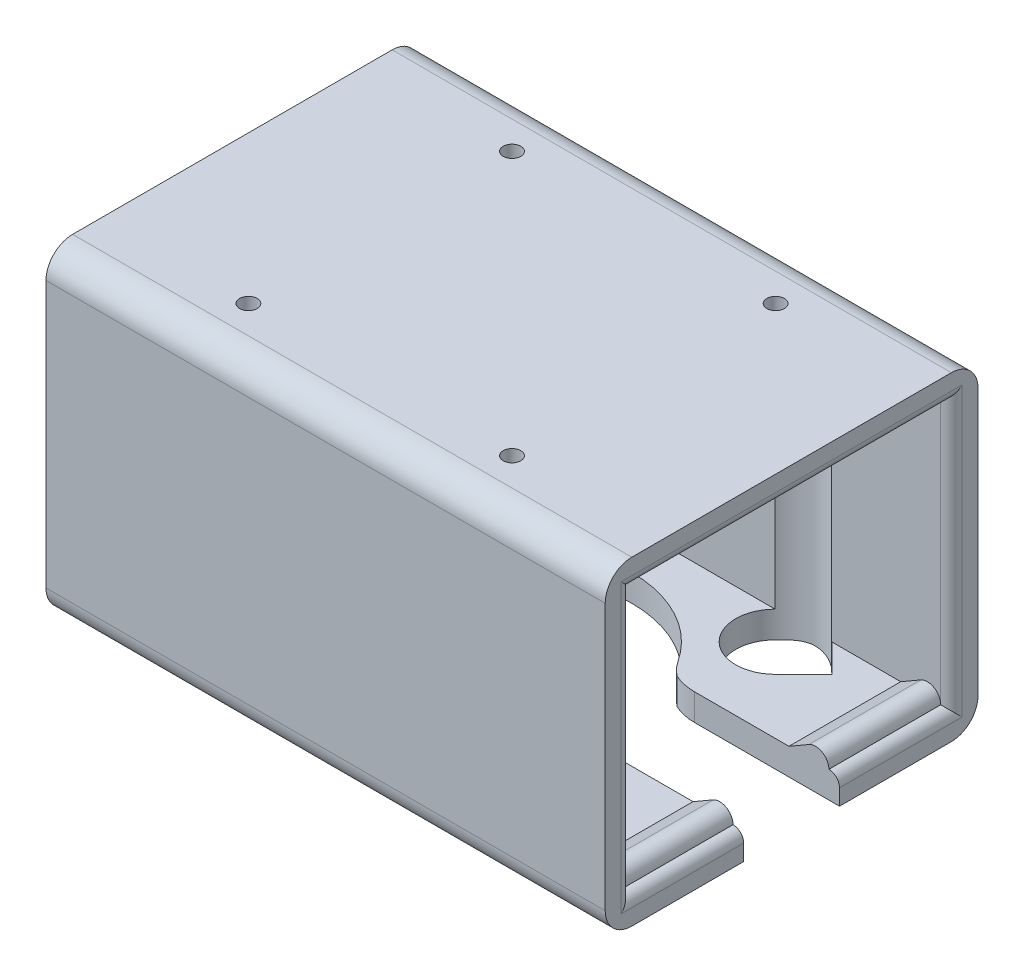
SolidWorks part; units mm, degrees
ref_plane "前视基准面" through (0, 0, 0) normal (0, 0, 1) x (1, 0, 0)
ref_plane "上视基准面" through (0, 0, 0) normal (0, 1, 0) x (1, 0, 0)
ref_plane "右视基准面" through (0, 0, 0) normal (1, 0, 0) x (0, 0, -1)
other "Configuration Table"
sketch "草图1" plane through (0, 0, 0) normal (0, 1, 0) x (1, 0, 0)
  line L0 (47.5, 30) -> (47.5, -30)
  line L1 (-47.5, -30) -> (47.5, -30)
  line L2 (-47.5, -30) -> (-47.5, 30)
  line L3 (-47.5, 30) -> (47.5, 30)
  line L5 (-47.5, -30) -> (47.5, 30) construction
  line L6 (-47.5, 30) -> (47.5, -30) construction
  line L7 (-20, -9) -> (20, -9)
  line L8 (-20, -9) -> (-20, 9)
  line L9 (-20, 9) -> (20, 9)
  line L10 (20, -9) -> (20, 9)
  line L11 (-20, -9) -> (20, 9) construction
  line L12 (-20, 9) -> (20, -9) construction
  line L17 (47.5, 30) -> (47.5, 35)
  line L18 (12.4677, 9) -> (47.5, 9)
  line L19 (12.4677, 9) -> (12.4677, -9)
  line L20 (12.4677, -9) -> (47.5, -9)
  line L21 (47.5, 9) -> (47.5, -9)
  line L22 (52.5, -35) -> (-52.5, -35)
  line L23 (52.5, -35) -> (52.5, 35)
  line L24 (52.5, 35) -> (-52.5, 35)
  line L25 (-52.5, -35) -> (-52.5, 35)
  line L26 (52.5, -35) -> (-52.5, 35) construction
  line L27 (52.5, 35) -> (-52.5, -35) construction
  line L28 (25.5014, 9) -> (52.5, 9)
  line L29 (25.5014, 9) -> (25.5014, -9)
  line L30 (25.5014, -9) -> (52.5, -9)
  line L31 (52.5, 9) -> (52.5, -9)
  line L32 (47.5, -30) -> (47.5, -35)
  line L33 (47.5, 30) -> (52.5, 30)
  line L34 (47.5, -30) -> (52.5, -30)
  point P0 (0, 0)
  point P6 (0, 0)
  point P11 (20, 0)
  point P16 (0, 0)
  dimension "D1" = 95
  dimension "D2" = 60
  dimension "D3" = 20
  dimension "D4" = 18
  dimension "D5" = 5
  dimension "D6" = 5
extrude "凸台-拉伸1" add sketch "草图1" along normal blind 5 contours L20 L7 L8 L9 L18 L0 L3 L2 L1 | L30 L0 L1 L2 L3 L28 L23 L24 L25 L22 | L17 L33 L23 L24 | L34 L32 L22 L23 | L33 L0 L28 L23 | L0 L34 L23 L30 region at (50, 0, -19.5) region at (46.3764, 0, -19.5) region at (0, 0, -31.2207) region at (50, 0, -32.5) region at (50, 0, 19.5) region at (50, 0, 32.5)
sketch "草图3" plane through (0, 5, 0) normal (0, 1, 0) x (1, 0, 0)
  line L0 (52.5, 9) -> (52.5, 35) construction
  line L1 (-52.5, 35) -> (52.5, 35)
  line L2 (-52.5, 35) -> (-52.5, 30)
  line L3 (-52.5, 30) -> (52.5, 30)
  line L4 (52.5, 35) -> (52.5, 30)
  line L5 (52.5, -35) -> (-52.5, -35) construction
  line L6 (-52.5, 35) -> (-47.5, 35)
  line L7 (-52.5, 35) -> (-52.5, -35)
  line L8 (-52.5, -35) -> (-47.5, -35)
  line L9 (-47.5, 35) -> (-47.5, -35)
  line L11 (-52.5, -30) -> (52.5, -30)
  line L12 (-52.5, -30) -> (-52.5, -35)
  line L13 (-52.5, -35) -> (52.5, -35)
  line L14 (52.5, -30) -> (52.5, -35)
  line M11 (52.5, 9) -> (52.5, 35)
  line M12 (52.5, 35) -> (-52.5, 35)
  line M13 (-52.5, 35) -> (-52.5, -35)
  line M14 (-52.5, -35) -> (52.5, -35)
  line M15 (52.5, -35) -> (52.5, -9)
  dimension "D1" = 5
  dimension "D2" = 5
  dimension "D3" = 5
extrude "凸台-拉伸2" add sketch "草图3" along normal blind 55 contours L9 L3 M12 M11 | L9 L1 L3 M13 | L11 L9 L3 M13 | L11 L9 M14 M15 | L11 L7 L9 M14 region at (-50, 5, -32.5) region at (2.5, 5, -32.5) region at (-50, 5, 0) region at (-50, 5, 32.5) region at (2.5, 5, 32.5)
sketch "草图4" plane through (-47.5, 0, 0) normal (1, 0, 0) x (0, 0, -1)
  line L0 (30, 60) -> (30, 5) construction
  line L1 (-30, 60) -> (30, 60)
  line L2 (-30, 60) -> (-30, 55)
  line L3 (-30, 55) -> (30, 55)
  line L4 (30, 60) -> (30, 55)
  dimension "D1" = 5
extrude "凸台-拉伸3" add sketch "草图4" along normal blind 100
sketch "草图5" plane through (0, 0, 0) normal (0, -1, 0) x (1, 0, 0)
  line L0 (0, 22.5) -> (22.5, 9)
  line L1 (-20, 9) -> (52.5, 9) construction
  line L2 (0, -22.5) -> (22.5, -9)
  line L3 (-20, -9) -> (52.5, -9) construction
  line L4 (22.5, -9) -> (22.5, 9)
  circle A0 centre (0, 0) radius 22.5
  line M3 (52.5, -9) -> (-20, -9)
  line M4 (-20, -9) -> (-20, 9)
  line M5 (-20, 9) -> (52.5, 9)
  dimension "D1" = 45
extrude "切除-拉伸1" cut sketch "草图5" against normal up to next contours L2 A0 L0 M3 M4 M5 | A0 L0 M5 | A0 L2 M3 | L0 A0 | L2 A0 region at (10.5905, 0, 17.6509) region at (9.6058, 0, 16.0097) region at (21.0019, 0, 9.5257) region at (10.5905, 0, -17.6509) region at (21.0019, 0, -9.5257)
fillet "圆角2" radius 10 2 edges at (19.8529, 2.5, 10.5882) (22.5, 2.5, 9)
fillet "圆角3" radius 10 2 edges at (22.5, 2.5, -9) (19.8529, 2.5, -10.5882)
fillet "圆角4" radius 5 4 edges at (0, 60, -35) (0, 0, -35) (0, 0, 35) (0, 60, 35)
fillet "圆角5" radius 2 5 edges at (52.5, 30, -30) (52.5, 30, 30) (52.5, 55, 0) (52.5, 5, 19.5) (52.5, 5, -19.5)
sketch "草图6" plane through (0, 55, 0) normal (0, -1, 0) x (1, 0, 0)
  line L1 (-24.75, -24.75) -> (24.75, -24.75)
  line L2 (-24.75, -24.75) -> (-24.75, 24.75)
  line L3 (-24.75, 24.75) -> (24.75, 24.75)
  line L4 (24.75, -24.75) -> (24.75, 24.75)
  line L5 (-24.75, -24.75) -> (24.75, 24.75) construction
  line L6 (-24.75, 24.75) -> (24.75, -24.75) construction
  circle A0 centre (-24.75, 24.75) radius 1.65
  circle A1 centre (24.75, 24.75) radius 1.65
  circle A2 centre (24.75, -24.75) radius 1.65
  circle A3 centre (-24.75, -24.75) radius 1.65
  point P0 (0, 0)
  dimension "D3" = 3.3
  dimension "D4" = 3.3
  dimension "D5" = 3.3
  dimension "D6" = 3.3
  dimension "D1" = 49.5
  dimension "D2" = 49.5
extrude "切除-拉伸2" cut sketch "草图6" against normal up to next contours A0 | A3 | A2 | A1
sketch "草图7" plane through (0, 0, 0) normal (0, -1, 0) x (1, 0, 0)
  line L0 (24.75, 24.75) -> (30.1061, 30)
  line L1 (-24.75, -24.75) -> (24.75, -24.75)
  line L2 (-24.75, -24.75) -> (-24.75, 24.75)
  line L3 (-24.75, 24.75) -> (24.75, 24.75)
  line L4 (24.75, -24.75) -> (24.75, 24.75)
  line L5 (-24.75, -24.75) -> (24.75, 24.75) construction
  line L6 (-24.75, 24.75) -> (24.75, -24.75) construction
  line L7 (52.5, 30) -> (-52.5, 30) construction
  line L8 (30.1061, 30) -> (35.2521, 24.75)
  line L9 (24.75, 24.75) -> (30, 19.3939)
  line L10 (30, 19.3939) -> (35.2521, 24.75)
  line L11 (-24.75, 24.75) -> (-19.4467, 30.0533)
  line L12 (-19.4467, 30.0533) -> (-14.1434, 24.75)
  line L13 (-24.75, 24.75) -> (-19.4467, 19.4467)
  line L14 (-19.4467, 19.4467) -> (-14.1434, 24.75)
  line L15 (-24.75, -24.75) -> (-19.4467, -19.4467)
  line L16 (-19.4467, -19.4467) -> (-14.1434, -24.75)
  line L17 (-24.75, -24.75) -> (-19.4467, -30.0533)
  line L18 (-19.4467, -30.0533) -> (-14.1434, -24.75)
  line L19 (24.75, -24.75) -> (30.0533, -19.4467)
  line L20 (30.0533, -19.4467) -> (35.3566, -24.75)
  line L21 (24.75, -24.75) -> (30.0533, -30.0533)
  line L22 (30.0533, -30.0533) -> (35.3566, -24.75)
  line L23 (24.75, -24.75) -> (35.3566, -24.75)
  circle A0 centre (-24.75, 24.75) radius 7.5
  circle A1 centre (24.75, 24.75) radius 7.5
  circle A2 centre (24.75, -24.75) radius 7.5
  circle A3 centre (-24.75, -24.75) radius 7.5
  point P0 (0, 0)
  line M20 (-52.5, -30) -> (52.5, -30)
  line M30 (52.5, 30) -> (-52.5, 30)
  dimension "D3" = 15
  dimension "D4" = 15
  dimension "D5" = 15
  dimension "D6" = 15
  dimension "D1" = 49.5
  dimension "D2" = 49.5
  dimension "D7" = 45
  dimension "D8" = 45
extrude "切除-拉伸3" cut sketch "草图7" against normal blind 50 contours A3 L1 L16 | A3 L18 L1 M20 | A3 L1 L17 M20 | L1 A3 L15 | L2 A3 L17 M20 | A3 L17 M20 | L15 A3 L2 | L4 A2 L1 | L1 A2 L21 M20 | A2 L21 M20 | A2 L23 L21 M20 | A2 L22 L23 M20 | A2 L23 L20 | L23 A2 L19 | L19 A2 L4 | A1 L3 L0 M30 | A1 M30 | L3 A1 L4 | L4 A1 L9 | L10 A1 L0 L9 | A1 L10 L8 | A0 L14 L3 | A0 L3 L12 M30 | L3 A0 L11 M30 | L13 A0 L3 | L2 A0 L13 | A0 L2 L11 M30 | L11 A0 M30 region at (22.7784, 0, 27.5264) region at (21.5669, 0, 21.5669) region at (26.5933, 0, 20.2362) region at (29.2514, 0, 24.705) region at (32.9604, 0, 24.7516) region at (24.75, 0, 30.9127) region at (-16.5126, 0, 23.3367) region at (-16.5126, 0, 26.1633) region at (26.6146, 0, -20.2484) region at (21.5669, 0, -21.5669) region at (-20.2484, 0, 22.8854) region at (-20.2485, 0, 26.6142) region at (-22.8854, 0, 20.2484) region at (22.7475, 0, -27.5223) region at (29.2515, 0, -26.6142) region at (29.2516, 0, -22.8854) region at (32.9874, 0, -23.3367) region at (-24.7509, 0, 30.9128) region at (-27.3084, 0, 24.7182) region at (24.7491, 0, -30.9128) region at (32.9874, 0, -26.1633) region at (-16.5126, 0, -26.1633) region at (-16.5126, 0, -23.3367) region at (-22.8854, 0, -20.2484) region at (-27.3084, 0, -24.7182) region at (-20.2485, 0, -26.6142) region at (-20.2484, 0, -22.8854) region at (-24.7509, 0, -30.9128)
sketch "草图9" plane through (0, 0, 30) normal (0, 0, -1) x (-1, 0, 0)
  line L0 (-30.1061, 5) -> (-50.5, 5) construction
  line L1 (-50.5, 5) -> (-45.5, 5)
  line L2 (-48, 5) -> (-46.75, 7.1651)
  line L3 (-46.75, 7.1651) -> (-43, 5)
  line L4 (-52.5, 5) -> (52.5, 5) construction
  line L5 (-43, 5) -> (-48, 5)
  arc A0 (-50.5, 5) -> (-45.5, 5) centre (-48, 5) cw
  point P6 (-46.9012, 7.2456)
  line M1 (-50.5, 5) -> (-30.1061, 5)
  dimension "D1" = 2.5
  dimension "D2" = 30
  dimension "D3" = 60
extrude "凸台-拉伸4" add sketch "草图9" along normal blind 60 contours L3 A0 M1 | A0 L2 L1 | A0 L2 M1 region at (48.6892, 6.1937, 30) region at (46.6217, 5.7958, 30) region at (44.8386, 5.6084, 30)
sketch "草图10" plane through (0, 5, 0) normal (0, -1, 0) x (1, 0, 0)
  line L1 (43, 9) -> (50.5, 9)
  line L2 (43, 9) -> (43, -9)
  line L3 (43, -9) -> (50.5, -9)
  line L4 (50.5, 9) -> (50.5, -9)
extrude "切除-拉伸4" cut sketch "草图10" against normal blind 5
